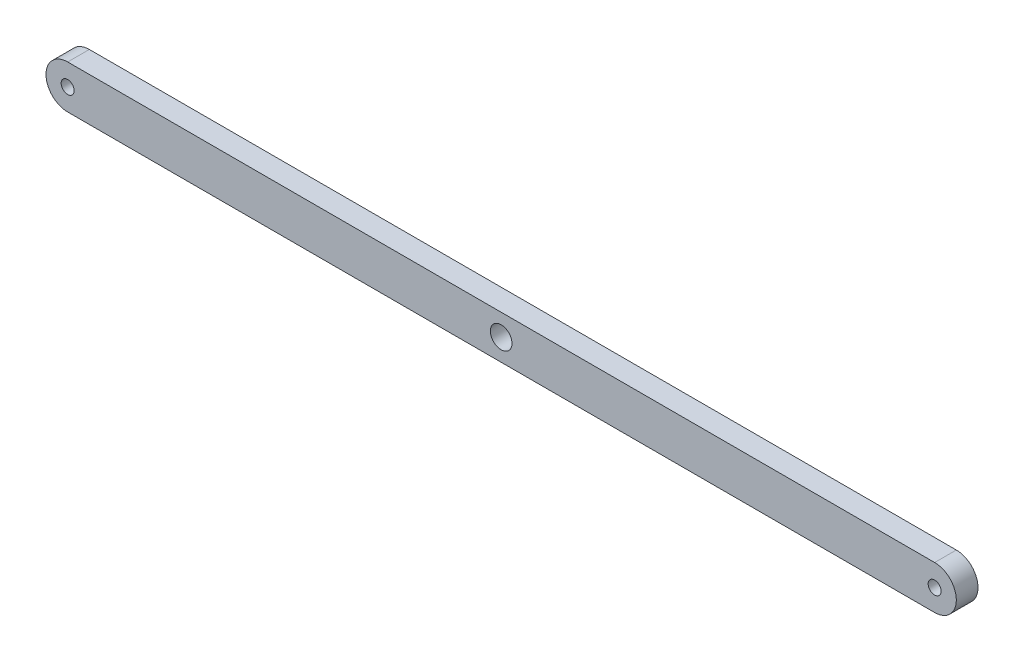
SolidWorks part; units mm, degrees
ref_plane "Piano frontale" through (0, 0, 0) normal (0, 0, 1) x (1, 0, 0)
ref_plane "Piano superiore" through (0, 0, 0) normal (0, 1, 0) x (1, 0, 0)
ref_plane "Piano destro" through (0, 0, 0) normal (1, 0, 0) x (0, 0, -1)
sketch "Sketch1" plane through (0, 0, 0) normal (0, 0, 1) x (1, 0, 0)
  line L0 (-1000, 0) -> (1000, 0) construction
  line L1 (-1000, 50) -> (1000, 50)
  line L2 (-1000, -50) -> (1000, -50)
  arc A0 (-1000, 50) -> (-1000, -50) centre (-1000, 0) ccw
  arc A1 (1000, -50) -> (1000, 50) centre (1000, 0) ccw
  point P3 (0, 0)
  dimension "D1" = 2000
  dimension "D2" = 100
extrude "Boss-Extrude1" add sketch "Sketch1" along normal mid plane 50
sketch "Sketch2" plane through (0, 0, 25) normal (0, 0, 1) x (1, 0, 0)
  circle A0 centre (-1000, 0) radius 15
  circle A1 centre (1000, 0) radius 15
  dimension "D1" = 30
extrude "Cut-Extrude1" cut sketch "Sketch2" against normal through all
sketch "Sketch3" plane through (0, 0, 0) normal (0, 0, 1) x (1, 0, 0)
  circle A0 centre (0, 0) radius 25
  dimension "D1" = 50
extrude "Cut-Extrude2" cut sketch "Sketch3" against normal through all both and the other way through all
ref_axis "Axis1" through (0, 0, -25) along (0, 0, 1)
ref_axis "Axis2" through (-1000, 0, -25) along (0, 0, 1)
ref_axis "Axis3" through (1000, 0, -25) along (0, 0, 1)
ref_point "Point1"
ref_point "Point2"
